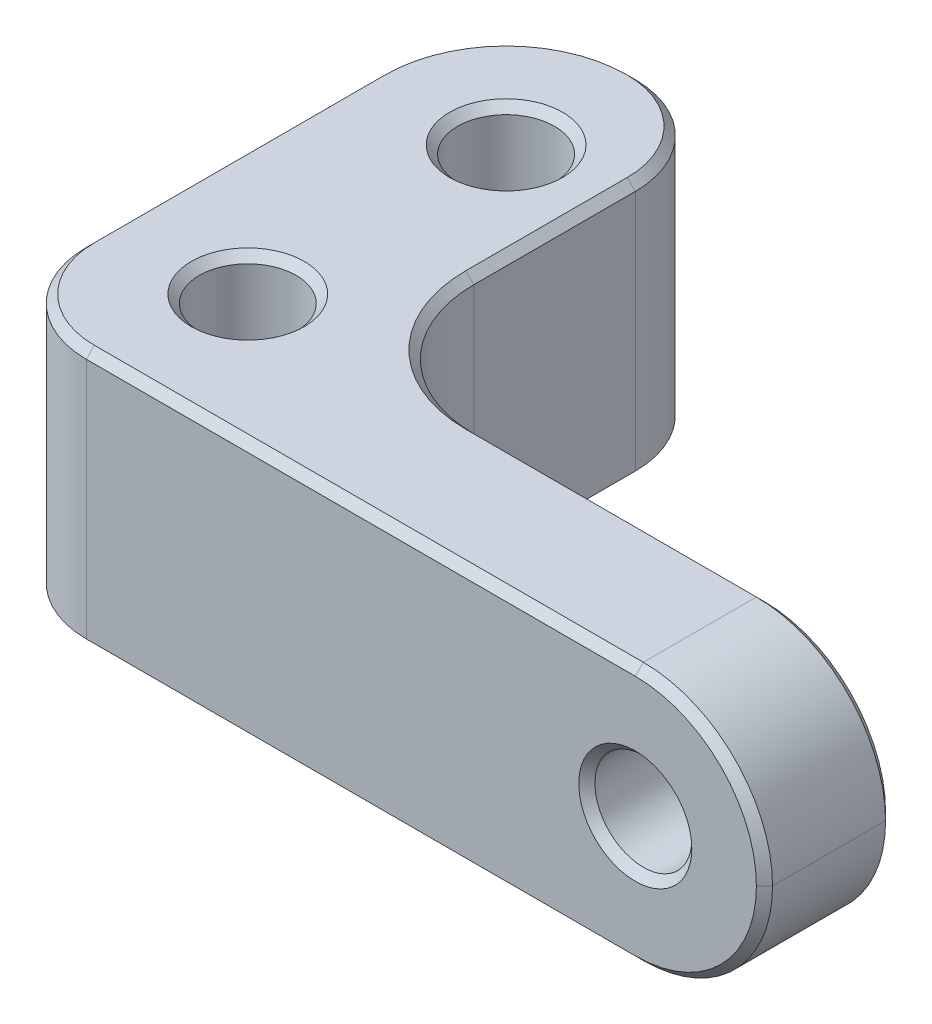
SolidWorks part; units mm, degrees
ref_plane "Front Plane" through (0, 0, 0) normal (0, 0, 1) x (1, 0, 0)
ref_plane "Top Plane" through (0, 0, 0) normal (0, 1, 0) x (1, 0, 0)
ref_plane "Right Plane" through (0, 0, 0) normal (1, 0, 0) x (0, 0, -1)
sketch "Sketch1" plane through (0, 0, 0) normal (0, 1, 0) x (1, 0, 0)
  line L0 (-6.35, -6.35) -> (31.75, -6.35)
  line L1 (31.75, -6.35) -> (31.75, 0)
  line L2 (31.75, 0) -> (4.7625, 0)
  line L3 (4.7625, 0) -> (4.7625, 19.05)
  line L4 (4.7625, 19.05) -> (-6.35, 19.05)
  line L5 (-6.35, 19.05) -> (-6.35, -6.35)
  circle A0 centre (0, 0) radius 2.3813
  circle A1 centre (0, 12.7) radius 2.3813
  dimension "D8" = 4.7625
  dimension "D9" = 4.7625
  dimension "D1" = 12.7
  dimension "D2" = 6.35
  dimension "D3" = 6.35
  dimension "D4" = 4.7625
  dimension "D5" = 6.35
  dimension "D6" = 38.1
  dimension "D7" = 6.35
extrude "Boss-Extrude1" add sketch "Sketch1" along normal mid plane 12.7
sketch "Sketch2" plane through (0, 0, 6.35) normal (0, 0, 1) x (1, 0, 0)
  circle A0 centre (25.4, 0) radius 2.3813
  point P2 (0, 0)
  dimension "D2" = 4.7625
  dimension "D1" = 25.4
extrude "Cut-Extrude1" cut sketch "Sketch2" against normal through all both and the other way through all
fillet "Fillet1" radius 6.35 4 edges at (-6.35, 0, -19.05) (4.7625, 0, 0) (31.75, -6.35, 3.175) (31.75, 6.35, 3.175)
fillet "Fillet2" radius 4.7625 2 edges at (-6.35, 0, 6.35) (4.7625, 0, -19.05)
chamfer "Chamfer1" distance 0.3969 angle 45 26 edges at (23.0187, 0, 6.35) (27.7812, 0, 0) (0, -6.35, -10.3187) (0, -6.35, 2.3813) (0, 6.35, -10.3187) (3.3676, -6.35, -17.6551) (-4.4901, -6.35, -17.1901) (4.7625, -6.35, -10.3187) (-6.35, -6.35, -5.5562) (6.6224, -6.35, -1.8599) (-4.9551, -6.35, 4.9551) (18.2563, -6.35, 0) (11.9062, -6.35, 6.35) (29.8901, -4.4901, 0) (29.8901, -4.4901, 6.35) (29.8901, 4.4901, 0) (29.8901, 4.4901, 6.35) (18.2563, 6.35, 0) (6.6224, 6.35, -1.8599) (4.7625, 6.35, -10.3187) (3.3676, 6.35, -17.6551) (-4.4901, 6.35, -17.1901) (11.9062, 6.35, 6.35) (-4.9551, 6.35, 4.9551) (-6.35, 6.35, -5.5562) (0, 6.35, 2.3813)
